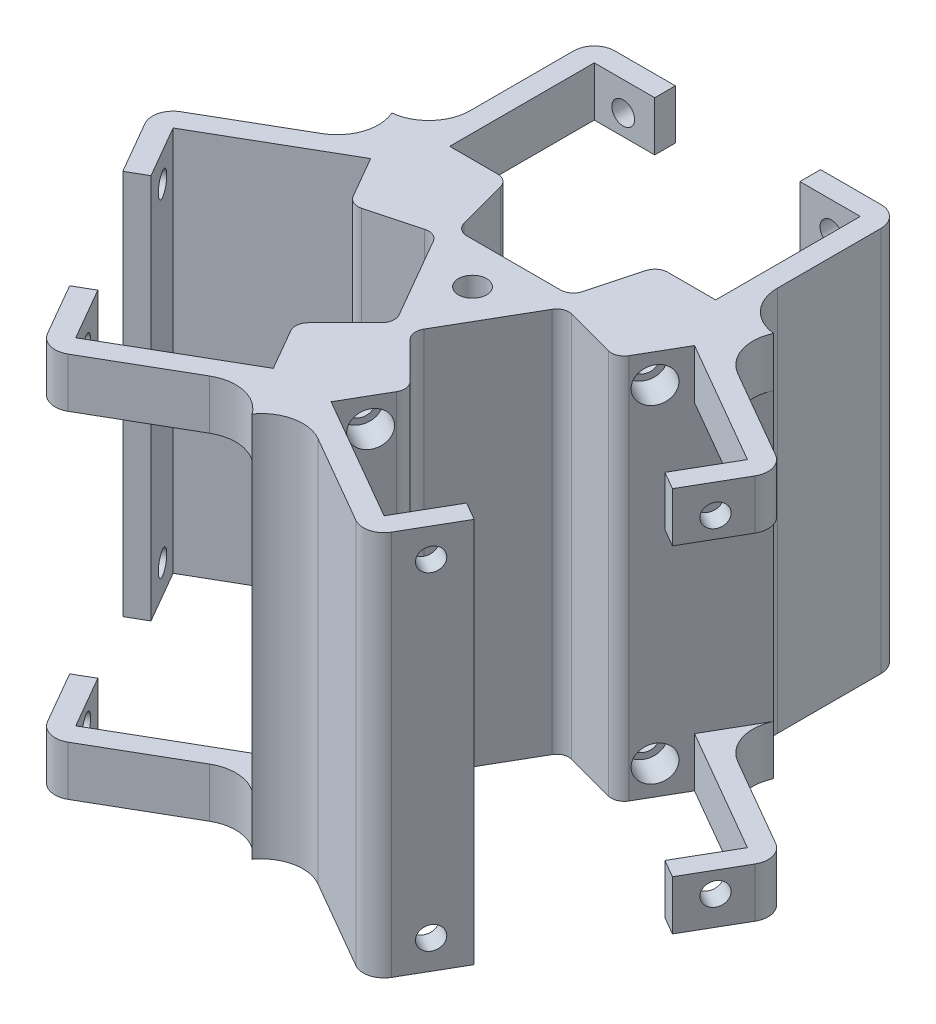
SolidWorks part; units mm, degrees
ref_plane "Alzado" through (0, 0, 0) normal (0, 0, 1) x (1, 0, 0)
ref_plane "Planta" through (0, 0, 0) normal (0, 1, 0) x (1, 0, 0)
ref_plane "Vista lateral" through (0, 0, 0) normal (1, 0, 0) x (0, 0, -1)
sketch "Croquis1" plane through (0, 0, 0) normal (0, 1, 0) x (1, 0, 0)
  line L0 (0, 50.8) -> (0, -50.8) construction
  line L1 (-50.8, 0) -> (50.8, 0) construction
  line L2 (0, 0) -> (-35.921, -35.921) construction
  line L3 (0, 0) -> (35.921, -35.921) construction
  line L10 (0, -17.5) -> (-15.1554, 8.75) construction
  line L11 (-15.1554, 8.75) -> (15.1554, 8.75) construction
  line L12 (15.1554, 8.75) -> (0, -17.5) construction
  line L13 (-1.2978, -16.7522) -> (-15.1813, 7.2027) construction
  line L14 (1.2978, -16.7522) -> (15.1813, 7.2027) construction
  line L15 (-13.8835, 9.4549) -> (13.8835, 9.4549) construction
  line L16 (1.6964, -16.0645) -> (13.335, -27.7031)
  line L17 (13.335, -27.7031) -> (0, -50.8)
  line L18 (0, -50.8) -> (-13.335, -27.7031)
  line L19 (-13.335, -27.7031) -> (-1.6964, -16.0645)
  line L20 (-17.3241, 25.4) -> (-13.0641, 9.5013)
  line L21 (-43.9941, 25.4) -> (-17.3241, 25.4)
  line L22 (-30.6591, 2.3031) -> (-43.9941, 25.4)
  line L23 (-14.7604, 6.5631) -> (-30.6591, 2.3031)
  line L24 (30.6591, 2.3031) -> (14.7604, 6.5631)
  line L25 (43.9941, 25.4) -> (30.6591, 2.3031)
  line L26 (17.3241, 25.4) -> (43.9941, 25.4)
  line L27 (13.0641, 9.5013) -> (17.3241, 25.4)
  line L28 (-14.7604, 6.5631) -> (-1.6964, -16.0645)
  line L29 (1.6964, -16.0645) -> (14.7604, 6.5631)
  line L30 (-13.0641, 9.5013) -> (13.0641, 9.5013)
  line L31 (-43.9941, 25.4) -> (0, -50.8) construction
  line L32 (43.9941, 25.4) -> (0, -50.8) construction
  line L33 (-43.9941, 25.4) -> (43.9941, 25.4) construction
  circle A0 centre (0, 0) radius 50.8 construction
  circle A7 centre (0, 0) radius 17.5 construction
  circle A8 centre (-13.8835, 7.9549) radius 1.5 construction
  circle A9 centre (13.8835, 7.9549) radius 1.5 construction
  circle A10 centre (0, -16) radius 1.5 construction
  arc A11 (-15.1813, 7.2027) -> (-13.8835, 9.4549) centre (-13.8835, 7.9549) cw construction
  arc A12 (15.1813, 7.2027) -> (13.8835, 9.4549) centre (13.8835, 7.9549) ccw construction
  arc A13 (1.2978, -16.7522) -> (-1.2978, -16.7522) centre (0, -16) cw construction
  arc A14 (-15.1813, 7.2027) -> (-13.8835, 9.4549) centre (-13.8835, 7.9549) cw construction
  arc A15 (13.8835, 9.4549) -> (15.1813, 7.2027) centre (13.8835, 7.9549) cw construction
  arc A16 (-1.2978, -16.7522) -> (1.2978, -16.7522) centre (0, -16) ccw construction
  circle A17 centre (0, 0) radius 76.2 construction
  point P45 (0, 0)
  dimension "D1" = 101.6
  dimension "D6" = 13.8835
  dimension "D9" = 3
  dimension "D5" = 3
  dimension "D4" = 35
  dimension "D10" = 152.4
  dimension "D2" = 45
  dimension "D3" = 45
  dimension "D7" = 26.67
extrude "Saliente-Extruir1" add sketch "Croquis1" along normal blind 88.9
sketch "Croquis4" plane through (0, 88.9, 0) normal (0, 1, 0) x (1, 0, 0)
  circle A0 centre (0, 0) radius 3.25
  dimension "D1" = 6.5
extrude "Cortar-Extruir1" cut sketch "Croquis4" against normal through all
fillet "Redondeo6" radius 3 5 edges at (-14.7604, 44.45, -6.5631) (1.6964, 44.45, 16.0645) (-1.6964, 44.45, 16.0645) (-13.0641, 44.45, -9.5013) (13.0641, 44.45, -9.5013)
fillet "Redondeo7" radius 3 6 edges at (-17.3241, 44.45, -25.4) (-30.6591, 44.45, -2.3031) (17.3241, 44.45, -25.4) (-13.335, 44.45, 27.7031) (30.6591, 44.45, -2.3031) (13.335, 44.45, 27.7031)
scale "Escala2" scale about centroid uniform scaling yes scale factor 1.05
sketch "Croquis9" plane through (0, 91.1225, 0) normal (0, 1, 0) x (1, 0, 0)
  line L9 (0, 76.2) -> (0, -76.2) construction
  line L10 (76.2, 0) -> (-76.2, 0) construction
  line L41 (-37.1934, 26.6702) -> (-37.1934, 61.6702)
  line L42 (-69.5041, -2.9545) -> (-39.1932, 14.5455)
  line L43 (-20.607, 26.6702) -> (-46.1934, 26.6702) construction
  line L44 (-32.1934, 66.6702) -> (-17.5643, 66.6702)
  line L45 (-17.5643, 66.6702) -> (-17.5643, 61.6702)
  line L46 (-17.5643, 61.6702) -> (-32.1934, 61.6702)
  line L47 (-32.1934, 61.6702) -> (-32.1934, 26.6702)
  line L48 (-32.1934, 26.6702) -> (-37.1934, 26.6702)
  line L49 (32.1934, 61.6702) -> (32.1934, 26.6702)
  line L50 (17.5643, 61.6702) -> (32.1934, 61.6702)
  line L51 (17.5643, 66.6702) -> (17.5643, 61.6702)
  line L52 (32.1934, 66.6702) -> (17.5643, 66.6702)
  line L53 (37.1934, 26.6702) -> (37.1934, 61.6702)
  line L54 (32.1934, 26.6702) -> (37.1934, 26.6702)
  line L55 (39.1937, 14.5452) -> (41.6937, 18.8753)
  line L56 (41.6937, 18.8753) -> (72.0046, 1.3753)
  line L57 (73.8347, -5.4548) -> (66.5202, -18.124)
  line L58 (66.5202, -18.124) -> (62.1901, -15.624)
  line L59 (62.1901, -15.624) -> (69.5046, -2.9548)
  line L60 (69.5046, -2.9548) -> (39.1937, 14.5452)
  line L61 (37.3112, -58.7154) -> (7.0003, -41.2154)
  line L62 (7.0003, -41.2154) -> (4.5003, -45.5455)
  line L63 (4.5003, -45.5455) -> (34.8112, -63.0455)
  line L64 (41.6414, -61.2154) -> (48.9559, -48.5462)
  line L65 (48.9559, -48.5462) -> (44.6258, -46.0462)
  line L66 (44.6258, -46.0462) -> (37.3112, -58.7154)
  line L79 (-39.1937, 14.5452) -> (-41.6937, 18.8753) [skipped]
  line L80 (-39.1932, 14.5455) -> (-41.6932, 18.8756)
  line L81 (-41.6937, 18.8753) -> (-72.0046, 1.3753) [skipped]
  line L83 (-41.6932, 18.8756) -> (-72.0041, 1.3756)
  line L85 (-69.5046, -2.9548) -> (-39.1937, 14.5452) [skipped]
  line L86 (-62.1901, -15.624) -> (-69.5046, -2.9548) [skipped]
  line L87 (-66.5202, -18.124) -> (-62.1901, -15.624) [skipped]
  line L88 (-73.8347, -5.4548) -> (-66.5202, -18.124) [skipped]
  line L89 (-73.8342, -5.4545) -> (-66.5197, -18.1237)
  line L90 (-66.5197, -18.1237) -> (-62.1896, -15.6237)
  line L91 (-62.1896, -15.6237) -> (-69.5041, -2.9545)
  line L92 (-46.1934, 26.6702) -> (-33.4002, 4.5117) construction
  line L93 (-7.0003, -41.2154) -> (-4.5003, -45.5455) [skipped]
  line L94 (-4.5003, -45.5455) -> (-34.8112, -63.0455) [skipped]
  line L95 (-41.6414, -61.2154) -> (-48.9559, -48.5462) [skipped]
  line L96 (-48.9559, -48.5462) -> (-44.6258, -46.0462) [skipped]
  line L97 (-44.6258, -46.0462) -> (-37.3112, -58.7154) [skipped]
  line L98 (-37.3112, -58.7154) -> (-7.0003, -41.2154) [skipped]
  line L99 (-6.9998, -41.2151) -> (-4.4998, -45.5452)
  line L100 (-4.4998, -45.5452) -> (-34.8107, -63.0452)
  line L101 (-41.6408, -61.2151) -> (-48.9554, -48.5459)
  line L102 (-48.9554, -48.5459) -> (-44.6253, -46.0459)
  line L103 (-44.6253, -46.0459) -> (-37.3107, -58.7151)
  line L104 (-37.3107, -58.7151) -> (-6.9998, -41.2151)
  line L105 (-12.7928, -31.1813) -> (0.0004, -53.3398) construction
  circle A0 centre (0, 0) radius 101.6 construction
  circle A1 centre (0, 0) radius 76.2 construction
  arc A8 (-37.1934, 61.6702) -> (-32.1934, 66.6702) centre (-32.1934, 61.6702) cw
  arc A9 (37.1934, 61.6702) -> (32.1934, 66.6702) centre (32.1934, 61.6702) ccw
  arc A10 (72.0046, 1.3753) -> (73.8347, -5.4548) centre (69.5046, -2.9548) cw
  arc A11 (34.8112, -63.0455) -> (41.6414, -61.2154) centre (37.3112, -58.7154) ccw
  arc A14 (-72.0046, 1.3753) -> (-73.8347, -5.4548) centre (-69.5046, -2.9548) ccw [skipped]
  arc A15 (-72.0041, 1.3756) -> (-73.8342, -5.4545) centre (-69.5041, -2.9545) ccw
  arc A16 (-34.8112, -63.0455) -> (-41.6414, -61.2154) centre (-37.3112, -58.7154) cw [skipped]
  arc A17 (-34.8107, -63.0452) -> (-41.6408, -61.2151) centre (-37.3107, -58.7151) cw
  point P55 (0.0002, 0.0003)
  point P56 (-1.3626, -0.7865)
  point P58 (0, 0)
  point P61 (0.0002, 0.0003)
  dimension "D1" = 152.4
  dimension "D2" = 203.2
  dimension "D3" = 5
  dimension "D9" = 2
  dimension "D4" = 9
  dimension "D5" = 35
  dimension "D6" = 3
  dimension "D7" = 2
sketch "Croquis12" plane through (0, 91.1225, 0) normal (0, 1, 0) x (1, 0, 0)
  line L0 (0, 101.6) -> (0, -101.6) construction
  circle A0 centre (0, 0) radius 76.2 construction
  circle A1 centre (0, 0) radius 101.6 construction
  dimension "D1" = 152.4
  dimension "D2" = 203.2
extrude "Saliente-Extruir2" add sketch "Croquis9" against normal through all
sketch "Croquis14" plane through (0, 0, -66.6702) normal (0, 0, -1) x (-1, 0, 0)
  line L0 (-32.1934, -2.2225) -> (-32.1934, 91.1225) construction
  line L1 (17.5643, 91.1225) -> (32.1934, 91.1225) construction
  circle A0 centre (25.1934, 84.1225) radius 2.75
  circle A1 centre (25.1934, 4.7775) radius 2.75
  circle A2 centre (-25.1934, 4.7775) radius 2.75
  circle A3 centre (-25.1934, 84.1225) radius 2.75
  dimension "D1" = 5.5
  dimension "D2" = 7
  dimension "D3" = 7
  dimension "D4" = 7
  dimension "D5" = 7
  dimension "D6" = 7
  dimension "D7" = 7
extrude "Cortar-Extruir2" cut sketch "Croquis14" against normal blind 10
sketch "Croquis15" plane through (0, 0, -26.6702) normal (0, 0, -1) x (-1, 0, 0)
  line L0 (32.1934, -2.2225) -> (32.1934, 91.1225) construction
  line L1 (-32.1934, -2.2225) -> (-20.6078, -2.2225) construction
  line L2 (-32.1934, 91.1225) -> (-20.6078, 91.1225) construction
  circle A0 centre (-25.1934, 4.7775) radius 4.25
  circle A1 centre (25.1934, 4.7775) radius 4.25
  circle A2 centre (-25.1934, 84.1225) radius 4.25
  circle A3 centre (25.1934, 84.1225) radius 4.25
  dimension "D1" = 8.5
  dimension "D2" = 7
  dimension "D3" = 7
  dimension "D4" = 7
  dimension "D5" = 7
  dimension "D6" = 7
  dimension "D7" = 7
extrude "Cortar-Extruir3" cut sketch "Croquis15" against normal blind 7.5
sketch "Croquis16" plane through (0, 0, -19.1702) normal (0, 0, -1) x (-1, 0, 0)
  circle A0 centre (-25.1934, 4.7775) radius 2.775
  circle A1 centre (25.1934, 4.7775) radius 2.775
  circle A2 centre (25.1934, 84.1225) radius 2.775
  circle A3 centre (-25.1934, 84.1225) radius 2.775
  dimension "D1" = 5.55
extrude "Cortar-Extruir4" cut sketch "Croquis16" against normal blind 3
pattern_circular "MatrizC7" count 3 over 360 about axis through (0.0004, -2.2225, -0.0002) along (0, 1, 0) of "Cortar-Extruir4", "Cortar-Extruir3"
sketch "Croquis17" plane through (18.5967, 0, -32.2104) normal (0.5, 0, -0.866) x (-0.866, 0, -0.5)
  line L0 (-26.6703, 91.1225) -> (-26.6703, -2.2225) construction
  line L1 (-26.6703, 79.1225) -> (-68.6703, 79.1225)
  line L2 (-26.6703, 79.1225) -> (-26.6703, 9.7775)
  line L3 (-26.6703, 9.7775) -> (-68.6703, 9.7775)
  line L4 (-68.6703, 79.1225) -> (-68.6703, 9.7775)
  line L5 (76.2, 91.1225) -> (-76.2, 91.1225) construction
  line L6 (-61.6702, -2.2225) -> (-26.6703, -2.2225) construction
  dimension "D1" = 42
  dimension "D2" = 12
  dimension "D3" = 12
extrude "Cortar-Extruir5" cut sketch "Croquis17" against normal blind 31
sketch "Croquis18" plane through (-37.1934, 0, 0) normal (-1, 0, 0) x (0, 0, 1)
  line L0 (-26.6702, 91.1225) -> (-26.6702, -2.2225) construction
  line L1 (-26.6702, 79.1225) -> (-71.6702, 79.1225)
  line L2 (-26.6702, 79.1225) -> (-26.6702, 9.7775)
  line L3 (-26.6702, 9.7775) -> (-71.6702, 9.7775)
  line L4 (-71.6702, 79.1225) -> (-71.6702, 9.7775)
  line L5 (101.6, 91.1225) -> (-101.6, 91.1225) construction
  line L6 (-61.6702, -2.2225) -> (-26.6702, -2.2225) construction
  dimension "D1" = 12
  dimension "D2" = 12
  dimension "D3" = 45
extrude "Cortar-Extruir6" cut sketch "Croquis18" against normal blind 31
fillet "Redondeo8" radius 10 2 edges at (-37.1934, 85.1225, -26.6702) (-37.1934, 3.7775, -26.6702)
fillet "Redondeo9" radius 10 1 edges at (37.1934, 44.45, -26.6702)
fillet "Redondeo12" radius 10 1 edges at (4.5004, 44.45, 45.5456)
fillet "Redondeo13" radius 10 2 edges at (41.6938, 85.1225, -18.8753) (41.6938, 3.7775, -18.8753)
pattern_circular "MatrizC8" count 3 over 360 about axis through (0.0004, 91.1225, -0.0002) along (0, 1, 0) of "Cortar-Extruir6"
fillet "Redondeo14" radius 10 2 edges at (-4.4998, 3.7775, 45.5452) (-4.4998, 85.1225, 45.5452)
fillet "Redondeo16" radius 10 1 edges at (-41.6932, 44.45, -18.8756)
fillet "Redondeo17" radius 3 1 edges at (15.4988, 44.45, -6.8915)
sketch "Croquis20" plane through (-57.7375, 0, 33.3348) normal (-0.866, 0, 0.5) x (0.5, 0, 0.866)
  line L0 (32.1934, -2.2225) -> (32.1934, 9.7775) construction
  line L1 (-87.9882, 91.1225) -> (87.9882, 91.1225) construction
  circle A0 centre (25.1934, 4.7775) radius 2.78
  circle A1 centre (25.1934, 84.1225) radius 2.78
  circle A2 centre (-25.1934, 84.1225) radius 2.78
  circle A3 centre (-25.1934, 4.7775) radius 2.78
  dimension "D1" = 5.56
  dimension "D2" = 7
  dimension "D3" = 7
  dimension "D4" = 7
  dimension "D5" = 7
extrude "Cortar-Extruir7" cut sketch "Croquis20" against normal blind 10
sketch "Croquis21" plane through (57.7381, 0, 33.3351) normal (0.866, 0, 0.5) x (0.5, 0, -0.866)
  line L0 (17.5643, 91.1225) -> (32.1934, 91.1225) construction
  line L1 (-32.1934, -2.2225) -> (-32.1934, 91.1225) construction
  line L2 (-32.1934, -2.2225) -> (-17.5643, -2.2225) construction
  circle A0 centre (25.1934, 4.7775) radius 2.775
  circle A1 centre (25.1934, 84.1225) radius 2.775
  circle A2 centre (-25.1934, 84.1225) radius 2.775
  circle A3 centre (-25.1934, 4.7775) radius 2.775
  dimension "D1" = 5.55
  dimension "D2" = 7
  dimension "D3" = 7
  dimension "D4" = 7
  dimension "D5" = 7
extrude "Cortar-Extruir8" cut sketch "Croquis21" against normal blind 10
